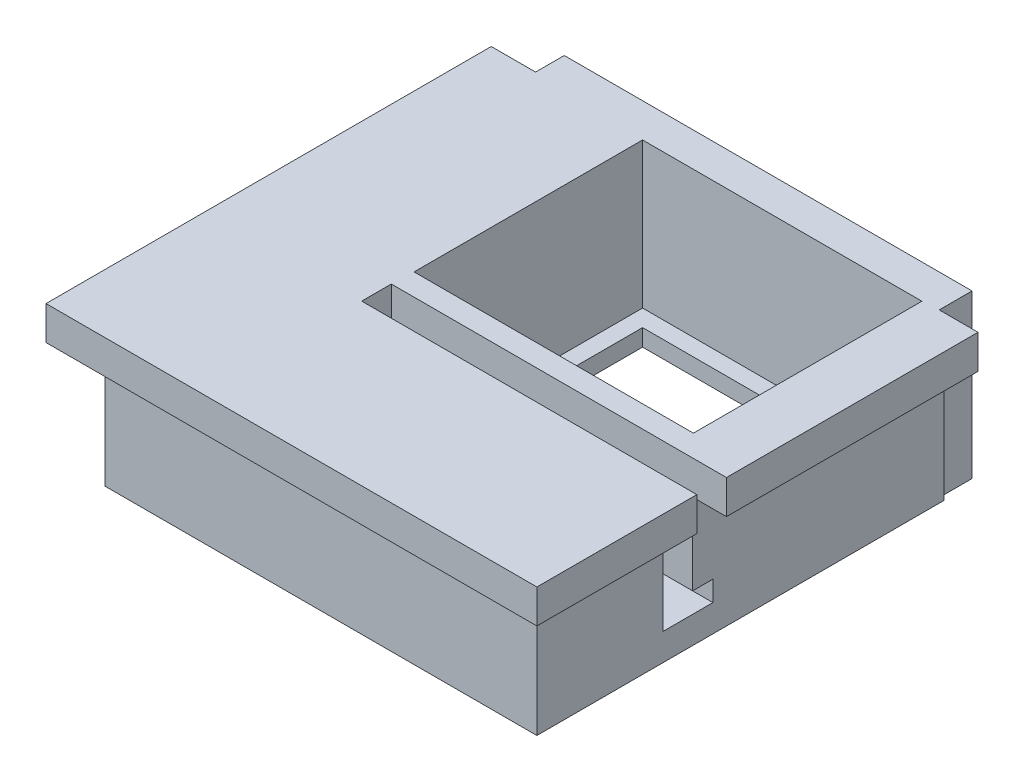
SolidWorks part; units mm, degrees
ref_plane "Front Plane" through (0, 0, 0) normal (0, 0, 1) x (1, 0, 0)
ref_plane "Top Plane" through (0, 0, 0) normal (0, 1, 0) x (1, 0, 0)
ref_plane "Right Plane" through (0, 0, 0) normal (1, 0, 0) x (0, 0, -1)
sketch "Sketch4" plane through (-9.897, 0, -25.5164) normal (0, 1, 0) x (1, 0, 0)
  line L1 (-26.0867, 10.5277) -> (-0.5867, 10.5277)
  line L2 (-26.0867, 10.5277) -> (-26.0867, -15.4723)
  line L3 (-26.0867, -15.4723) -> (-0.5867, -15.4723)
  line L4 (-0.5867, 10.5277) -> (-0.5867, -15.4723)
extrude "Boss-Extrude6" add sketch "Sketch4" along normal blind 9.6 separate body contours L1 L4 L3 L2
sketch "Sketch17" plane through (-9.897, 9.6, -25.5164) normal (0, 1, 0) x (1, 0, 0)
  line L1 (-26.0867, 10.5277) -> (-24.9695, 10.5277)
  line L2 (-26.0867, 10.5277) -> (-26.0867, 8.8322)
  line L3 (-26.0867, 8.8322) -> (-24.9695, 8.8322)
  line L4 (-24.9695, 10.5277) -> (-24.9695, 8.8322)
extrude "Cut-Extrude3" cut sketch "Sketch17" against normal blind 9.6
sketch "Sketch18" plane through (-9.897, 9.6, -25.5164) normal (0, 1, 0) x (1, 0, 0)
  line L0 (-0.5867, 10.5277) -> (-0.5867, -15.4723) construction
  line L1 (-0.5867, -6.2725) -> (-18.3871, -6.2725)
  line L2 (-0.5867, -6.2725) -> (-0.5867, -8.0225)
  line L3 (-0.5867, -8.0225) -> (-18.3871, -8.0225)
  line L4 (-18.3871, -6.2725) -> (-18.3871, -8.0225)
extrude "Cut-Extrude10" cut sketch "Sketch18" against normal blind 8
sketch "Sketch19" plane through (-10.4837, 0, 0) normal (1, 0, 0) x (0, 0, -1)
  line L1 (19.2439, 1.6) -> (20.4439, 1.6)
  line L2 (19.2439, 1.6) -> (19.2439, 2.8)
  line L5 (19.2439, 2.8) -> (20.4439, 2.8)
  line L6 (20.4439, 1.6) -> (20.4439, 2.8)
sketch "Sketch20" plane through (0, 9.6, 0) normal (0, 1, 0) x (1, 0, 0)
  line L1 (-11.7307, 34.0364) -> (-28.2307, 34.0364)
  line L2 (-11.7307, 34.0364) -> (-11.7307, 20.5364)
  line L3 (-11.7307, 20.5364) -> (-28.2307, 20.5364)
  line L4 (-28.2307, 34.0364) -> (-28.2307, 20.5364)
extrude "Cut-Extrude13" cut sketch "Sketch20" against normal blind 10.5
sketch "Sketch21" plane through (0, 9.6, 0) normal (0, 1, 0) x (1, 0, 0)
  line L1 (-10.4837, 36.0442) -> (-10.7751, 36.0442)
  line L2 (-10.4837, 36.0442) -> (-10.4837, 34.1041)
  line L3 (-10.4837, 34.1041) -> (-10.7751, 34.1041)
  line L4 (-10.7751, 36.0442) -> (-10.7751, 34.1041)
extrude "Cut-Extrude14" cut sketch "Sketch21" against normal blind 10.5
sketch "Sketch22" plane through (-10.4837, 0, 0) normal (1, 0, 0) x (0, 0, -1)
  line L0 (19.2439, 1.6) -> (19.2439, 9.6) construction
  line L1 (34.1041, 9.6) -> (19.2439, 9.6)
  line L2 (34.1041, 9.6) -> (34.1041, 7.5976)
  line L3 (34.1041, 7.5976) -> (19.2439, 7.5976)
  line L4 (19.2439, 9.6) -> (19.2439, 7.5976)
extrude "Boss-Extrude7" add sketch "Sketch22" along normal blind 2
sketch "Sketch23" plane through (-10.4837, 0, 0) normal (1, 0, 0) x (0, 0, -1)
  line L0 (10.0442, 9.6) -> (10.0442, 0) construction
  line L1 (17.4939, 9.6) -> (10.0442, 9.6)
  line L2 (17.4939, 9.6) -> (17.4939, 7.605)
  line L3 (17.4939, 7.605) -> (10.0442, 7.605)
  line L4 (10.0442, 9.6) -> (10.0442, 7.605)
extrude "Boss-Extrude8" add sketch "Sketch23" along normal blind 2
sketch "Sketch24" plane through (0, 0, -10.0442) normal (0, 0, 1) x (1, 0, 0)
  line L1 (-35.9837, 9.6) -> (-8.4837, 9.6)
  line L2 (-35.9837, 9.6) -> (-35.9837, 7.605)
  line L3 (-35.9837, 7.605) -> (-8.4837, 7.605)
  line L4 (-8.4837, 9.6) -> (-8.4837, 7.605)
extrude "Boss-Extrude9" add sketch "Sketch24" along normal blind 2
sketch "Sketch25" plane through (-35.9837, 0, 0) normal (-1, 0, 0) x (0, 0, 1)
  line L1 (-34.3486, 9.6) -> (-8.0442, 9.6)
  line L2 (-34.3486, 9.6) -> (-34.3486, 7.605)
  line L3 (-34.3486, 7.605) -> (-8.0442, 7.605)
  line L4 (-8.0442, 9.6) -> (-8.0442, 7.605)
extrude "Boss-Extrude10" add sketch "Sketch25" along normal blind 1.5
extrude "Cut-Extrude15" cut sketch "Sketch19" against normal blind 18.5 and the other way through all
sketch "Sketch26" plane through (-28.2307, 0, 0) normal (1, 0, 0) x (0, 0, -1)
  line L0 (34.0364, 0) -> (34.0364, 9.6) construction
  line L1 (20.5364, 0) -> (34.0364, 0)
  line L2 (20.5364, 0) -> (20.5364, 1)
  line L3 (20.5364, 1) -> (34.0364, 1)
  line L4 (34.0364, 0) -> (34.0364, 1)
extrude "Boss-Extrude11" add sketch "Sketch26" along normal blind 1
sketch "Sketch27" plane through (0, 0, -34.0364) normal (0, 0, 1) x (1, 0, 0)
  line L1 (-11.7307, 0) -> (-27.2307, 0)
  line L2 (-11.7307, 0) -> (-11.7307, 1)
  line L3 (-11.7307, 1) -> (-27.2307, 1)
  line L4 (-27.2307, 0) -> (-27.2307, 1)
extrude "Boss-Extrude12" add sketch "Sketch27" along normal blind 1
sketch "Sketch28" plane through (-11.7307, 0, 0) normal (-1, 0, 0) x (0, 0, 1)
  line L0 (-20.5364, 0) -> (-20.5364, 9.6) construction
  line L1 (-33.0364, 0) -> (-20.5364, 0)
  line L2 (-33.0364, 0) -> (-33.0364, 1)
  line L3 (-33.0364, 1) -> (-20.5364, 1)
  line L4 (-20.5364, 0) -> (-20.5364, 1)
extrude "Boss-Extrude13" add sketch "Sketch28" along normal blind 1
sketch "Sketch29" plane through (0, 0, -20.5364) normal (0, 0, -1) x (-1, 0, 0)
  line L1 (12.7307, 0) -> (27.2307, 0)
  line L2 (12.7307, 0) -> (12.7307, 1)
  line L3 (12.7307, 1) -> (27.2307, 1)
  line L4 (27.2307, 0) -> (27.2307, 1)
extrude "Boss-Extrude14" add sketch "Sketch29" along normal blind 1
